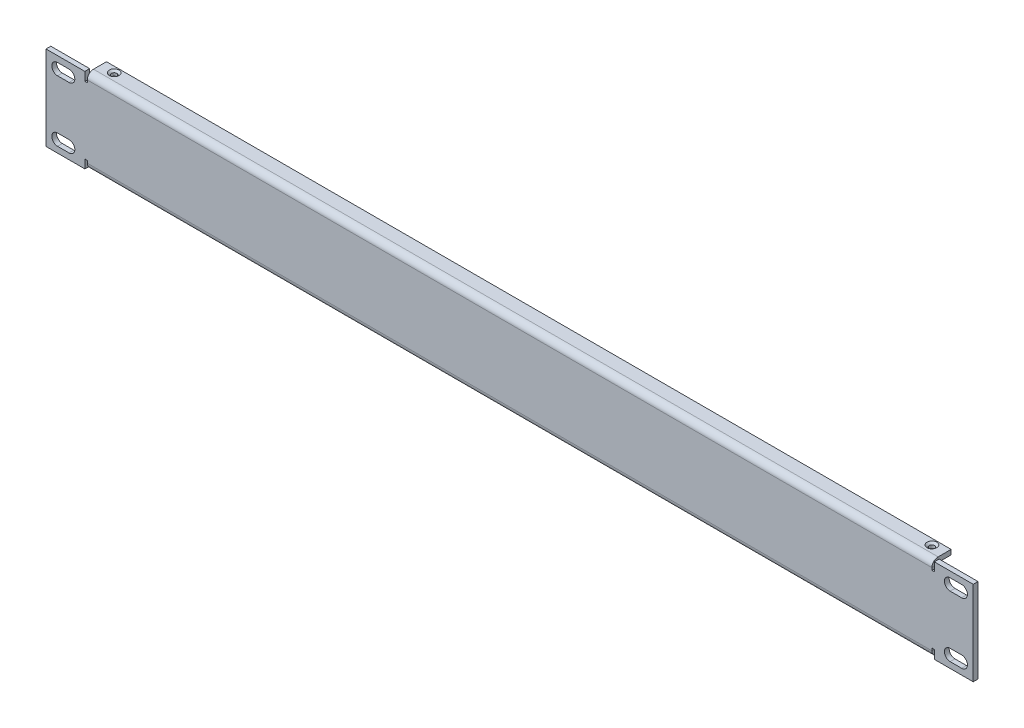
SolidWorks part; units mm, degrees
note: The reader was unsure of these and kept them because the rebuilt part matched: flange length of "Edge-Flange1".
ref_plane "Front Plane" through (0, 0, 0) normal (0, 0, 1) x (1, 0, 0)
ref_plane "Top Plane" through (0, 0, 0) normal (0, 1, 0) x (1, 0, 0)
ref_plane "Right Plane" through (0, 0, 0) normal (1, 0, 0) x (0, 0, -1)
sketch "Sketch1" plane through (0, 0, 0) normal (0, 0, 1) x (1, 0, 0)
  line L1 (0, 0) -> (-241.5, 0)
  line L2 (0, 0) -> (0, 22)
  line L3 (0, 22) -> (-241.5, 22)
  line L4 (-241.5, 0) -> (-241.5, 22)
  dimension "D1" = 22
  dimension "D2" = 241.5
sheet metal parameters "Sheet-Metal1" thickness 2.5 parameters "D1"=0.7366
base flange "Base-Flange1" sketch "Sketch1" thickness 2.5 reverse thickness direction no parameters "D1"=0.7366
edge flange "Edge-Flange1" sketch "Sketch12" flange angle 90 flange length 10 flange position material inside bend radius 0.7366 thickness 2.5 parameters "D6"=10
sketch "Sketch12" plane through (0, 22, -2.5) normal (0, 1, 0) x (1, 0, 0)
  line L0 (0, 0) -> (-241.5, 0) construction
  line L1 (0, 0) -> (-220, 0)
  line L2 (-220, 0) -> (-220, 7.5)
  line L3 (-220, 7.5) -> (0, 7.5)
  line L4 (0, 7.5) -> (0, 0)
  line L6 (-241.5, 0) -> (-241.5, -2.5) construction
  dimension "D1" = 21.5
bend "EdgeBend1" bend radius 0.7366 bend angle 90 parameters "D5"=1
sketch "Sketch13" plane through (0, 0, 0) normal (0, 0, 1) x (1, 0, 0)
  line L0 (-235.5, 15.9) -> (-229.5, 15.9) construction
  line L1 (-241.5, 0) -> (0, 0) construction
  line L2 (0, 0) -> (0, 18.7634) construction
  line L3 (-235.5, 18.9) -> (-229.5, 18.9)
  line L4 (-235.5, 12.9) -> (-229.5, 12.9)
  arc A0 (-235.5, 12.9) -> (-235.5, 18.9) centre (-235.5, 15.9) cw
  arc A1 (-229.5, 12.9) -> (-229.5, 18.9) centre (-229.5, 15.9) ccw
  point P0 (-232.5, 15.9)
  dimension "D1" = 15.9
  dimension "D2" = 232.5
extrude "Cut-Extrude1" cut sketch "Sketch13" against normal blind 2.5
hole_wizard "CSK for #3 Flat Head Machine Screw (100)1" positions "Sketch15" profile "Sketch14" countersink size "#3" standard "ANSI Inch" end condition up to next
sketch "Sketch15" plane through (0, 22, 0) normal (0, 1, 0) x (1, 0, 0)
  line L0 (-220, 10) -> (-220, 3.2366) construction
  line L1 (0, 10) -> (-220, 10) construction
  point P0 (-213, 7)
  dimension "D1" = 7
  dimension "D2" = 3
sketch "Sketch14" plane through (-213, 22, -7) normal (1, 0, 0) x (0, 0, 1)
  line L0 (0, 0) -> (0, 2.5)
  line L1 (0, 2.5) -> (1.397, 2.5)
  line L2 (1.397, 2.5) -> (1.397, 0.9484)
  line L3 (1.397, 0.9484) -> (2.5273, 0)
  line L5 (2.5273, 0) -> (0, 0)
  line L6 (-1.397, 0.9484) -> (-2.5273, 0) construction
  line L11 (0, -6.35) -> (0, 107.95) construction
  dimension "Thru Hole Dia." = 2.794
  dimension "Thru Hole Depth" = 2.5
  dimension "Near C'Sink Dia." = 5.0546
  dimension "Near C'Sink Angle" = 100
mirror "Mirror1" about plane through (0, 0, -2.5) normal (1, 0, 0) of bodies 104
mirror "Mirror2"
bend "MirrorBend1" bend radius 0.7366 bend angle 90 parameters "D5"=2
flat pattern "Flat-Pattern1" [suppressed]
sketch "Bend-Lines1" plane through (0, 0, 0) normal (0, 1, 0) x (1, 0, 0)
sketch3d "Bounding-Box1" [suppressed]
  line L0 (241.5, 0, 0) -> (0, 0, 0) construction
  line L1 (241.5, 22, 0) -> (0, 22, 0) construction
  line L2 (241.5, 0, 0) -> (241.5, 22, 0) construction
  line L3 (0, 0, 0) -> (0, 22, 0) construction
bend of the flat pattern "Flatten-<EdgeBend1>1"
bend of the flat pattern "Flatten-<MirrorBend1>1"
equation "\"RackUnitHeight\" = 44"
equation "\"RackUnitWidth\"= 483"
equation "\"RackUnitInnerWidth\"= 440"
equation "\"RackUnitMountingHoleHorizontalSpacing\"= 465"
equation "\"RackUnitMountingHoleVerticalSpacing\"= 15.90"
equation "\"D1@Sketch1\" = \"RackUnitHeight\" / 2"
equation "\"D2@Sketch1\"=\"RackUnitWidth\" / 2"
equation "\"D1@Sketch13\" = \"RackUnitMountingHoleVerticalSpacing\""
equation "\"D2@Sketch13\"=\"RackUnitMountingHoleHorizontalSpacing\" / 2"
equation "\"RackUnitHeight\"= 44"
